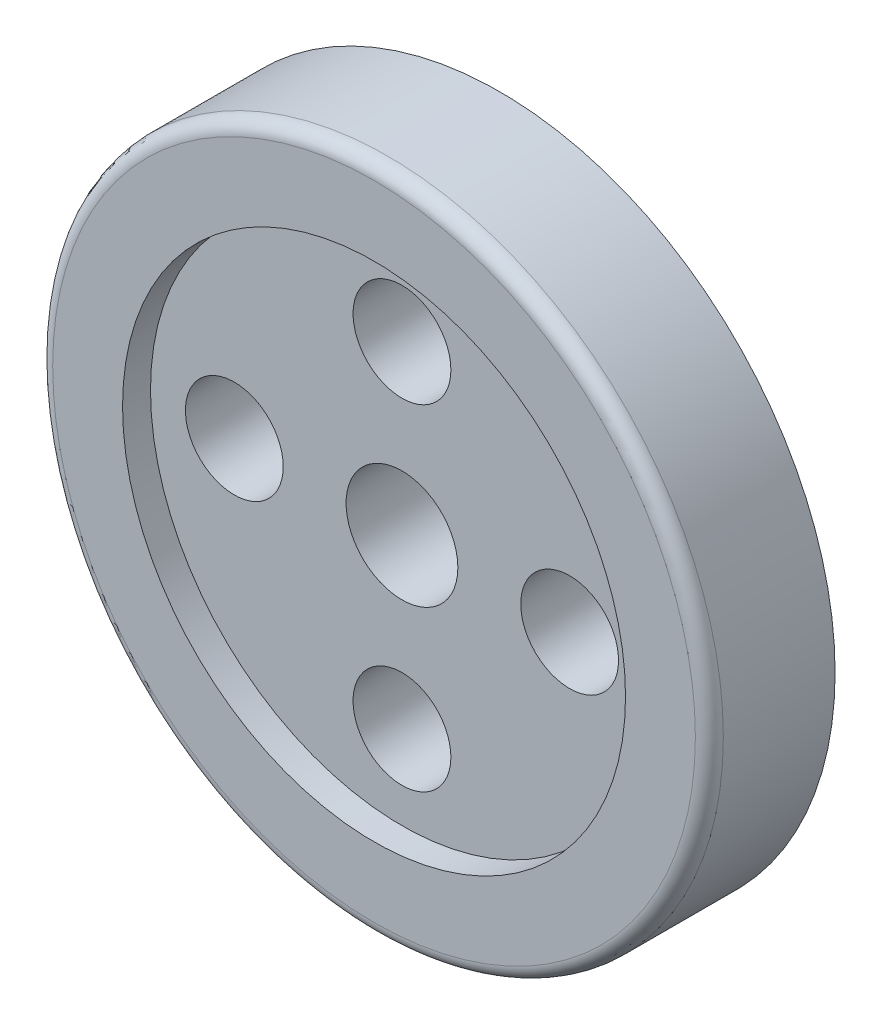
SolidWorks part; units mm, degrees
ref_plane "Front Plane" through (0, 0, 0) normal (0, 0, 1) x (1, 0, 0)
ref_plane "Top Plane" through (0, 0, 0) normal (0, 1, 0) x (1, 0, 0)
ref_plane "Right Plane" through (0, 0, 0) normal (1, 0, 0) x (0, 0, -1)
sketch "Sketch1" plane through (0, 0, 0) normal (0, 0, 1) x (1, 0, 0)
  line L0 (-39.8266, 0) -> (32.5854, 0) construction
  line L1 (0, 31.2956) -> (0, -35.5045) construction
  circle A0 centre (0, 0) radius 24
  circle A1 centre (0, 0) radius 16
  circle A2 centre (0, 0) radius 18
  circle A3 centre (0, 0) radius 12 construction
  circle A4 centre (0, 0) radius 4
  circle A5 centre (0, 12) radius 3.5
  circle A6 centre (-12, 0) radius 3.5
  circle A7 centre (0, -12) radius 3.5
  circle A8 centre (12, 0) radius 3.5
  dimension "D1" = 48
  dimension "D2" = 32
  dimension "D3" = 36
  dimension "D4" = 24
  dimension "D5" = 7
  dimension "D6" = 8
extrude "Boss-Extrude3" add sketch "Sketch1" along normal mid plane 9 contours A0 A2 region at (-23.3212, 0, 0)
extrude "Boss-Extrude4" add sketch "Sketch1<7>" against normal blind 7 from offset 2.5 contours A2 A1 | A1 A8 A7 A6 A5 A4 region at (-15.5475, 0, 0) region at (-17.4909, 0, 0)
sketch "Sketch1<7>" plane through (0, 0, 0) normal (0, 0, 1) x (1, 0, 0) same geometry as "Sketch1"
fillet "Fillet1" radius 1 1 edges at (24, 0, 4.5)
